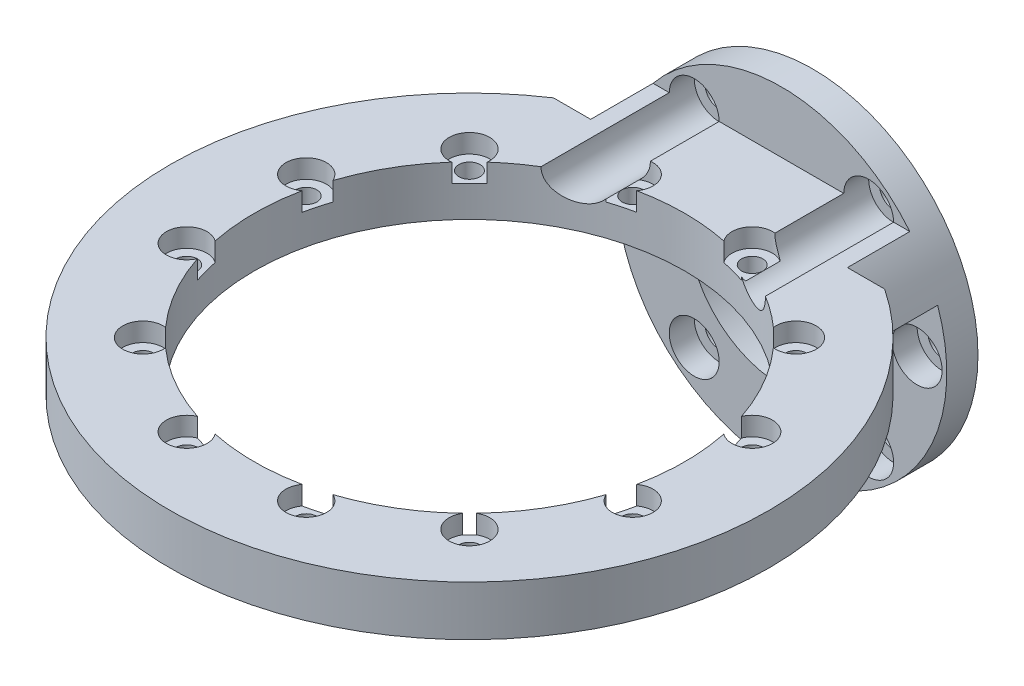
SolidWorks part; units mm, degrees
ref_plane "前视基准面" through (0, 0, 0) normal (0, 0, 1) x (1, 0, 0)
ref_plane "上视基准面" through (0, 0, 0) normal (0, 1, 0) x (1, 0, 0)
ref_plane "右视基准面" through (0, 0, 0) normal (1, 0, 0) x (0, 0, -1)
sketch "草图1" plane through (0, 0, 0) normal (0, 0, 1) x (1, 0, 0)
  circle A3 centre (0, 0) radius 26.5
extrude "凸台-拉伸1" add sketch "草图1" along normal blind 5
hole_wizard "M4 六角凹头盖的柱孔1" positions "3D草图2" profile "草图3" counterbore size "M4" standard "BSI" end condition through all
sketch3d "3D草图2"
  point P14 (-13.9806, 16.6615, 0)
  point P34 (-13.9806, 16.6615, 5)
  point P36 (13.9806, 16.6615, 5)
  point P38 (-21.75, 0, 5)
  point P40 (-13.9806, -16.6615, 5)
  point P42 (13.9806, -16.6615, 5)
  point P44 (21.75, 0, 5)
sketch "草图3" plane through (21.75, 0, 5) normal (1, 0, 0) x (0, -1, 0)
  line L0 (0, 0) -> (0, 5)
  line L1 (0, 5) -> (2.25, 5)
  line L3 (2.25, 5) -> (2.25, 4)
  line L4 (2.25, 4) -> (4, 4)
  line L5 (4, 4) -> (4, 0)
  line L7 (4, 0) -> (0, 0)
  line L11 (0, -6.35) -> (0, 107.95) construction
  dimension "通孔孔直径" = 4.5
  dimension "通孔孔深度" = 5
  dimension "柱形沉头孔直径" = 8
  dimension "柱形沉头孔深度" = 4
ref_plane "基准面1" through (0, 0, 5) normal (0, 0, 1) x (1, 0, 0)
sketch "参考" plane through (0, 0, 5) normal (0, 0, 1) x (1, 0, 0)
  line L12 (-20.7304, 8.7) -> (19.3146, 8.7) construction
ref_plane "基准面3" through (0, 8.7, 0) normal (0, -1, 0) x (1, 0, 0)
sketch "草图5" plane through (0, 8.7, 0) normal (0, -1, 0) x (1, 0, 0)
  line L0 (-26.5, 5) -> (-26.5, 14.9781)
  line L4 (26.5, 5) -> (26.5, 14.9781)
  line L9 (-26.5, 5) -> (26.5, 5)
  arc A4 (26.5, 14.9781) -> (-26.5, 14.9781) centre (0, 55) ccw
  point P0 (0, 0)
extrude "盘面" add sketch "草图5" against normal blind 8
sketch "草图6" plane through (0, 0, 5) normal (0, 0, 1) x (1, 0, 0)
  circle A0 centre (-13.9806, 16.6615) radius 4
  circle A1 centre (13.9806, 16.6615) radius 4
extrude "螺孔" cut sketch "草图6" along normal blind 22
sketch "草图8" plane through (0, 8.7, 0) normal (0, -1, 0) x (1, 0, 0)
  circle A1 centre (0, 55) radius 34.5
extrude "盘面切割" cut sketch "草图8" against normal through all
hole_wizard "M3 六角凹头盖的柱孔1" positions "3D草图3" profile "草图10" counterbore size "M3" standard "BSI" end condition through all
sketch3d "3D草图3"
  line L0 (0, 16.7, 55) -> (0, 8.7, 55) construction
  line L5 (0, 16.7, 55) -> (9.5763, 16.7, 19.2607)
  line L7 (0, 16.7, 55) -> (-9.5763, 16.7, 90.7393)
  line L11 (26.163, 16.7, 28.837) -> (0, 16.7, 55)
  line L17 (35.7393, 16.7, 45.4237) -> (0, 16.7, 55)
  line L19 (0, 16.7, 55) -> (35.7393, 16.7, 64.5763)
  line L21 (0, 16.7, 55) -> (26.6194, 16.7, 81.6194)
  line L22 (0, 16.7, 55) -> (-26.163, 16.7, 28.837)
  line L37 (0, 16.7, 55) -> (9.5763, 16.7, 90.7393)
  line L44 (-9.5763, 16.7, 19.2607) -> (0, 16.7, 55)
  line L54 (0, 16.7, 55) -> (-35.7393, 16.7, 45.4237)
  line L56 (0, 16.7, 55) -> (-26.163, 16.7, 81.163)
  line L68 (0, 16.7, 55) -> (-35.7393, 16.7, 64.5763)
  point P19 (9.5763, 16.7, 19.2607)
  point P34 (26.163, 16.7, 28.837)
  point P43 (35.7393, 16.7, 45.4237)
  point P46 (35.7393, 16.7, 64.5763)
  point P49 (26.6194, 16.7, 81.6194)
  point P169 (9.5763, 16.7, 90.7393)
  point P171 (-9.5763, 16.7, 90.7393)
  point P173 (-26.163, 16.7, 81.163)
  point P181 (-26.163, 16.7, 28.837)
  point P183 (-35.7393, 16.7, 45.4237)
  point P185 (-35.7393, 16.7, 64.5763)
  point P187 (-9.5763, 16.7, 19.2607)
sketch "草图10" plane through (-9.5763, 16.7, 19.2607) normal (1, 0, 0) x (0, 0, 1)
  line L0 (0, 0) -> (0, 43.2)
  line L1 (0, 43.2) -> (1.7, 43.2)
  line L3 (1.7, 43.2) -> (1.7, 3)
  line L4 (1.7, 3) -> (3.25, 3)
  line L5 (3.25, 3) -> (3.25, 0)
  line L7 (3.25, 0) -> (0, 0)
  line L11 (0, -6.35) -> (0, 107.95) construction
  dimension "通孔孔直径" = 3.4
  dimension "通孔孔深度" = 43.2
  dimension "柱形沉头孔直径" = 6.5
  dimension "柱形沉头孔深度" = 3
sketch "草图11" plane through (0, 0, 0) normal (0, 0, 1) x (1, 0, 0)
  line L0 (-25.0312, 8.7) -> (-29.0312, 8.7)
  line L1 (-29.15, 8.7) -> (29.15, 8.7) construction
  line L2 (-29.0312, 8.7) -> (-29.0312, 16.7)
  line L3 (48, 16.7) -> (-48, 16.7) construction
  line L4 (-29.0312, 16.7) -> (-20.5757, 16.7)
  line L6 (29.0312, 16.7) -> (20.5757, 16.7)
  line L7 (29.0312, 8.7) -> (29.0312, 16.7)
  line L8 (25.0312, 8.7) -> (29.0312, 8.7)
  arc A0 (-25.0312, 8.7) -> (25.0312, 8.7) centre (0, 0) ccw construction
  arc A1 (-25.0312, 8.7) -> (-20.5757, 16.7) centre (0, 0) cw
  arc A2 (25.0312, 8.7) -> (20.5757, 16.7) centre (0, 0) ccw
extrude "切除-拉伸1" cut sketch "草图11" along normal blind 15
sketch "草图12" plane through (0, 8.7, 0) normal (0, -1, 0) x (1, 0, 0)
  line L2 (39.2995, 79.0331) -> (30.6404, 73.9927)
  line L3 (40.2995, 32.8878) -> (31.6288, 37.8938)
  line L5 (25.4094, 16.6939) -> (19.8988, 25.0014)
  line L6 (39.2995, 31.1557) -> (30.6288, 36.1618)
  line L7 (31.6038, 72.2393) -> (40.2207, 77.2552)
  line L9 (-1, 96.0328) -> (-1, 90.9861)
  line L10 (1, 96.0328) -> (1, 101.0547)
  line L11 (1, 96.0328) -> (1, 90.9861)
  line L12 (-1, 96.0328) -> (-1, 101.0547)
  line L13 (-31.6038, 72.2393) -> (-40.2207, 77.2552)
  line L14 (-39.2995, 31.1557) -> (-30.6288, 36.1618)
  line L15 (-25.4094, 16.6939) -> (-19.8988, 25.0014)
  line L16 (-40.2995, 32.8878) -> (-31.6288, 37.8938)
  line L17 (-39.2995, 79.0331) -> (-30.6404, 73.9927)
  arc A9 (27.8489, 77.813) -> (22.813, 82.849) centre (26.6194, 81.6194) ccw
  arc A13 (12.9499, 88.5902) -> (5.5801, 90.5649) centre (9.5763, 90.7393) ccw
  arc A14 (33.5513, 42.0651) -> (35.5645, 49.4283) centre (35.7393, 45.4237) ccw
  arc A15 (35.5633, 60.5798) -> (33.59, 67.9502) centre (35.7393, 64.5763) ccw
  arc A16 (22.6075, 26.986) -> (27.9776, 32.4112) centre (26.163, 28.837) ccw
  arc A17 (12.9499, 88.5902) -> (22.813, 82.849) centre (0, 55) cw
  arc A18 (33.59, 67.9502) -> (31.6038, 72.2393) centre (0, 55) ccw
  arc A19 (35.5633, 60.5798) -> (35.5645, 49.4283) centre (0, 55) cw
  arc A20 (30.6288, 36.1618) -> (27.9776, 32.4112) centre (0, 55) cw
  arc A21 (22.6075, 26.986) -> (19.8988, 25.0014) centre (0, 55) cw
  arc A22 (5.5801, 90.5649) -> (1, 90.9861) centre (0, 55) ccw
  arc A23 (25.4094, 16.6939) -> (39.2995, 31.1557) centre (0, 55) ccw
  arc A24 (31.6288, 37.8938) -> (33.5513, 42.0651) centre (0, 55) ccw
  arc A25 (40.2995, 32.8878) -> (40.2207, 77.2552) centre (0, 55) ccw
  arc A26 (39.2995, 79.0331) -> (1, 101.0547) centre (0, 55) ccw
  arc A27 (30.6404, 73.9927) -> (27.8992, 77.8296) centre (0, 55) ccw
  arc A28 (-30.6404, 73.9927) -> (-27.8992, 77.8296) centre (0, 55) cw
  arc A29 (-39.2995, 79.0331) -> (-1, 101.0547) centre (0, 55) cw
  arc A30 (-40.2995, 32.8878) -> (-40.2207, 77.2552) centre (0, 55) cw
  arc A31 (-31.6288, 37.8938) -> (-33.5513, 42.0651) centre (0, 55) cw
  arc A32 (-25.4094, 16.6939) -> (-39.2995, 31.1557) centre (0, 55) cw
  arc A33 (-5.5801, 90.5649) -> (-1, 90.9861) centre (0, 55) cw
  arc A34 (-22.6075, 26.986) -> (-19.8988, 25.0014) centre (0, 55) ccw
  arc A35 (-30.6288, 36.1618) -> (-27.9776, 32.4112) centre (0, 55) ccw
  arc A36 (-35.5633, 60.5798) -> (-35.5645, 49.4283) centre (0, 55) ccw
  arc A37 (-33.59, 67.9502) -> (-31.6038, 72.2393) centre (0, 55) cw
  arc A38 (-12.9499, 88.5902) -> (-22.813, 82.849) centre (0, 55) ccw
  arc A39 (-22.6075, 26.986) -> (-27.9776, 32.4112) centre (-26.163, 28.837) cw
  arc A40 (-35.5633, 60.5798) -> (-33.59, 67.9502) centre (-35.7393, 64.5763) cw
  arc A41 (-33.5513, 42.0651) -> (-35.5645, 49.4283) centre (-35.7393, 45.4237) cw
  arc A42 (-12.9499, 88.5902) -> (-5.5801, 90.5649) centre (-9.5763, 90.7393) cw
  arc A43 (-27.8489, 77.813) -> (-22.813, 82.849) centre (-26.6194, 81.6194) cw
extrude "切除-拉伸2" cut sketch "草图12" against normal blind 5 contours A27 L2 A26 L10 L11 A22 A13 A17 A9 | L3 A25 L7 A18 A15 A19 A14 A24 | L5 A23 L6 A20 A16 A21 | A28 A43 A38 A42 A33 L9 L12 A29 L17 | A31 A41 A36 A40 A37 L13 A30 L16 | A34 A39 A35 L14 A32 L15 region at (19.8462, 8.7, 89.8632) region at (40.0107, 8.7, 55.079) region at (30.014, 8.7, 26.342) region at (-19.8462, 8.7, 89.8632) region at (-40.0107, 8.7, 55.079) region at (-30.014, 8.7, 26.342)
sketch "草图13" plane through (0, 0, 5) normal (0, 0, 1) x (1, 0, 0)
  line L0 (-20.7304, 8.7) -> (19.3146, 8.7) construction
  line L1 (-12.2192, 8.7) -> (12.2192, 8.7)
  arc A1 (-12.2192, 8.7) -> (12.2192, 8.7) centre (0, 0) ccw
extrude "切除-拉伸3" cut sketch "草图13" against normal blind 10
